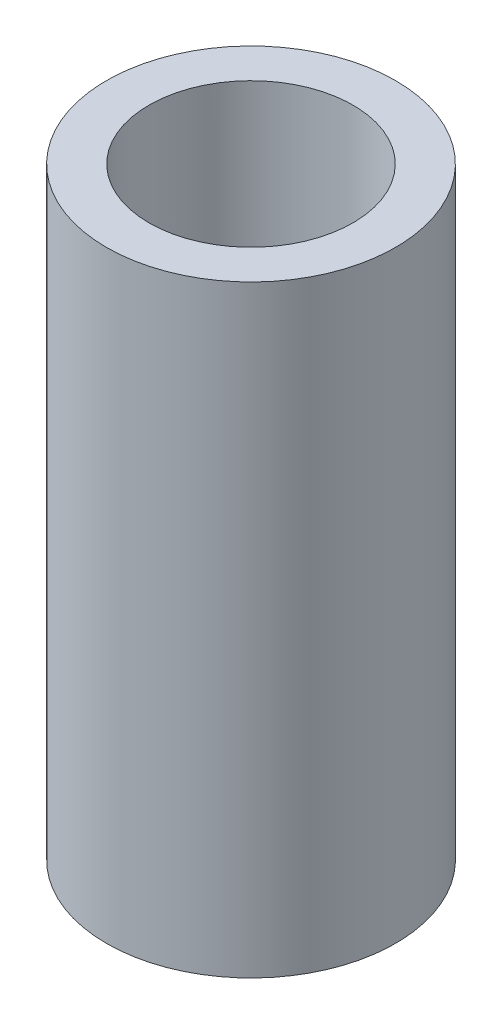
SolidWorks part; units mm, degrees
material "ABS"
ref_plane "Front Plane" through (0, 0, 0) normal (0, 0, 1) x (1, 0, 0)
ref_plane "Top Plane" through (0, 0, 0) normal (0, 1, 0) x (1, 0, 0)
ref_plane "Right Plane" through (0, 0, 0) normal (1, 0, 0) x (0, 0, -1)
sketch "Sketch1" plane through (0, 0, 0) normal (0, 1, 0) x (1, 0, 0)
  circle A0 centre (0, 0) radius 24
  circle A1 centre (0, 0) radius 34
  dimension "D1" = 48
  dimension "D2" = 68
extrude "Boss-Extrude1" add sketch "Sketch1" along normal blind 141.8
sketch "Sketch2" plane through (0, 0, 0) normal (1, 0, 0) x (0, 0, -1)
  line L1 (34, 141.8) -> (-34, 141.8) construction
  circle A0 centre (0, 24.6) radius 12.53
  circle A1 centre (0, 77.6) radius 12.53
  dimension "D1" = 25.06
  dimension "D2" = 25.06
  dimension "D3" = 64.2
  dimension "D5" = 53
extrude "Cut-Extrude1" cut sketch "Sketch2" against normal through all
